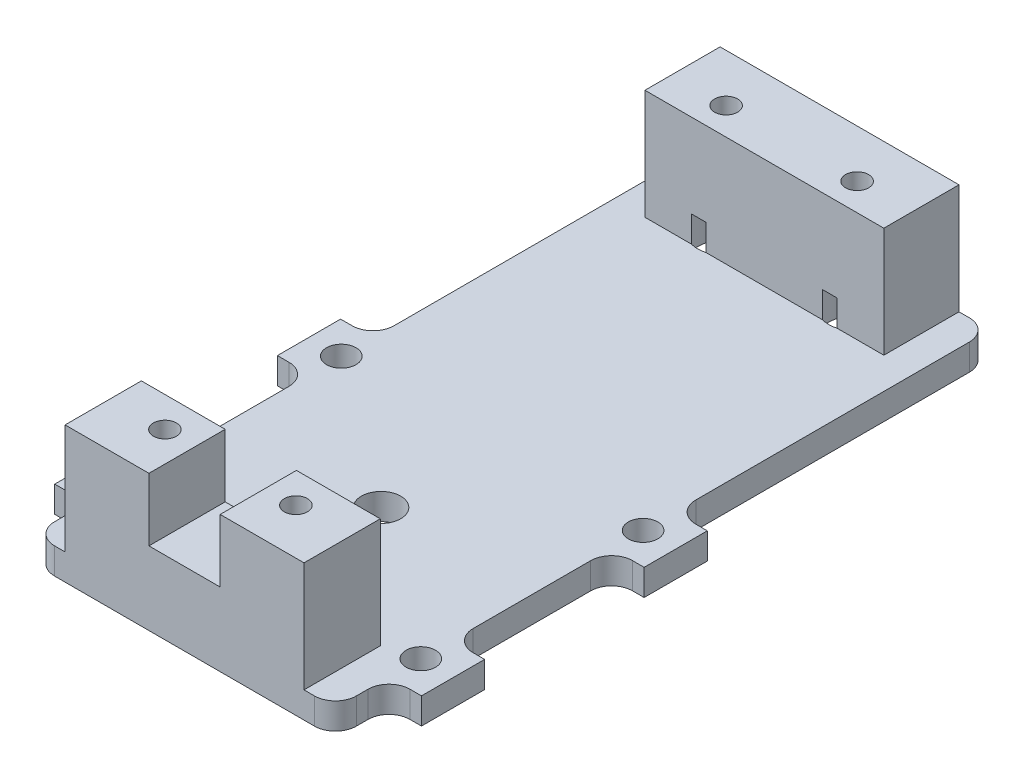
SolidWorks part; units mm, degrees
material "ABS"
ref_plane "Front Plane" through (0, 0, 0) normal (0, 0, 1) x (1, 0, 0)
ref_plane "Top Plane" through (0, 0, 0) normal (0, 1, 0) x (1, 0, 0)
ref_plane "Right Plane" through (0, 0, 0) normal (1, 0, 0) x (0, 0, -1)
sketch "Sketch1" plane through (0, 0, 0) normal (0, 1, 0) x (1, 0, 0)
  line L0 (18.288, -9.6647) -> (22.225, -9.6647)
  line L1 (-18.288, -23.8125) -> (18.288, -23.8125)
  line L2 (-18.288, -23.8125) -> (-18.288, -17.3228)
  line L3 (-18.288, 55.5625) -> (18.288, 55.5625)
  line L4 (18.288, -23.8125) -> (18.288, -17.3228)
  line L5 (-22.225, -17.3228) -> (-18.288, -17.3228)
  line L6 (-22.225, -17.3228) -> (-22.225, -9.6647)
  line L7 (-22.225, 17.3228) -> (-18.288, 17.3228)
  line L8 (22.225, -17.3228) -> (22.225, -9.6647)
  line L9 (0, 0.0043) -> (-31.7584, 0.0043) construction
  line L10 (-31.7584, 0.0043) -> (-18.288, -13.4661) construction
  line L11 (-22.225, -9.6647) -> (-18.288, -9.6647)
  line L12 (-18.288, 17.3228) -> (-18.288, 55.5625)
  line L13 (-22.225, 9.6647) -> (-18.288, 9.6647)
  line L14 (-18.288, -9.6647) -> (-18.288, 9.6647)
  line L15 (18.288, 9.6647) -> (22.225, 9.6647)
  line L17 (18.288, -9.6647) -> (18.288, 9.6647)
  line L18 (22.225, 9.6647) -> (22.225, 17.3228)
  line L19 (-22.225, 9.6647) -> (-22.225, 17.3228)
  line L20 (-18.288, -9.6647) -> (-18.288, 9.6647)
  line L21 (18.288, -9.6647) -> (18.288, 9.6647)
  line L22 (18.288, 17.3228) -> (18.288, 55.5625)
  line L23 (18.288, 17.3228) -> (22.225, 17.3228)
  line L24 (18.288, -17.3228) -> (22.225, -17.3228)
  line L25 (-31.7584, 0.0043) -> (-18.288, 13.4747) construction
  line L26 (0, -23.8125) -> (0, 0.0043) construction
  line L28 (-14.478, -13.8906) -> (14.478, -13.8906) construction
  line L29 (-14.478, -13.8906) -> (-14.478, 45.7994) construction
  line L30 (-14.478, 45.7994) -> (14.478, 45.7994) construction
  line L31 (14.478, -13.8906) -> (14.478, 45.7994) construction
  circle A0 centre (0, 0.0043) radius 2.3812
  circle A1 centre (7.9375, 49.7649) radius 3.429 construction
  circle A2 centre (-7.9375, 49.7649) radius 3.429 construction
  circle A3 centre (7.9375, -18.2563) radius 3.429 construction
  circle A4 centre (-7.9375, -18.2563) radius 3.429 construction
  point P4 (-7.9375, -18.2562)
  point P6 (0, 0)
  point P9 (7.9375, -18.2562)
  point P10 (-7.9375, 49.7649)
  point P11 (7.9375, 49.7649)
  point P31 (18.288, -13.4661)
  point P32 (18.288, 13.4747)
  point P47 (0.4762, -4.2035)
  dimension "D21" = 6.858
  dimension "D1" = 36.576
  dimension "D2" = 79.375
  dimension "D3" = 18.288
  dimension "D4" = 23.8125
  dimension "D5" = 18.2562
  dimension "D6" = 7.9375
  dimension "D9" = 5.5563
  dimension "D10" = 34.6456
  dimension "D11" = 44.45
  dimension "D12" = 19.3294
  dimension "D13" = 9.6647
  dimension "D14" = 19.05
  dimension "D15" = 19.05
  dimension "D16" = 90
  dimension "D17" = 28.956
  dimension "D18" = 14.478
  dimension "D19" = 59.69
  dimension "D20" = 13.8906
  dimension "D7" = 2
  dimension "D8" = 2
extrude "Boss-Extrude1" add sketch "Sketch1" along normal blind 3.175 contours L4 L24 L8 L0 L17 L15 L18 L23 L22 L3 L12 L7 L19 L13 L14 L11 L6 L5 L2 L1 L31 L28 L29 L30 region at (0, 0, -15.3322)
hole_wizard "9/64 (0.14063) Diameter Hole1" positions "Sketch5" profile "Sketch6" hole size "9/64" standard "Ansi Inch" end condition up to next
sketch "Sketch5" plane through (0, 0, 0) normal (0, -1, 0) x (1, 0, 0)
  point P4 (18.288, -13.4747)
  point P7 (18.288, 13.4661)
  point P35 (-18.288, -13.4704)
  point P37 (-18.288, 13.4704)
sketch "Sketch6" plane through (18.288, 0, -13.4747) normal (1, 0, 0) x (0, 0, -1)
  line L0 (0, 0) -> (0, 3.175)
  line L1 (0, 3.175) -> (1.786, 3.175)
  line L2 (1.786, 3.175) -> (1.786, 0)
  line L5 (1.786, 0) -> (0, 0)
  line L11 (0, -6.35) -> (0, 107.95) construction
  dimension "Thru Hole Dia." = 3.572
  dimension "Thru Hole Depth" = 3.175
fillet "Fillet1" radius 2.54 12 edges at (18.288, 1.5875, 23.8125) (18.288, 1.5875, 17.3228) (18.288, 1.5875, 9.6647) (18.288, 1.5875, -9.6647) (18.288, 1.5875, -17.3228) (18.288, 1.5875, -55.5625) (-18.288, 1.5875, -55.5625) (-18.288, 1.5875, -17.3228) (-18.288, 1.5875, -9.6647) (-18.288, 1.5875, 9.6647) (-18.288, 1.5875, 17.3228) (-18.288, 1.5875, 23.8125)
sketch "Sketch9" plane through (0, 0, 0) normal (0, 1, 0) x (1, 0, 0)
  line L0 (-18.288, 55.5625) -> (18.288, 55.5625) construction
  line L1 (-18.288, -23.8125) -> (18.288, -23.8125) construction
  line L5 (-14.478, -14.5696) -> (14.478, -14.5696)
  line L6 (-14.478, -14.5696) -> (-14.478, -23.8125)
  line L8 (-14.4653, 46.453) -> (14.4907, 46.453)
  line L9 (-14.4653, 46.453) -> (-14.4653, 55.5625)
  line L10 (-14.4653, 55.5625) -> (14.4907, 55.5625)
  line L11 (14.4907, 46.453) -> (14.4907, 55.5625)
  line L12 (-14.478, -23.8125) -> (14.478, -23.8125)
  line L13 (14.478, -14.5696) -> (14.478, -23.8125)
  circle A2 centre (-7.9375, -18.2562) radius 1.397
  circle A3 centre (7.9375, -18.2562) radius 1.397
  circle A4 centre (-7.9375, 49.7649) radius 1.397
  circle A5 centre (7.9375, 49.7649) radius 1.397
  dimension "D1" = 2.794
  dimension "D2" = 2.794
  dimension "D3" = 2.794
  dimension "D4" = 2.794
  dimension "D5" = 9.1095
  dimension "D7" = 28.956
  dimension "D8" = 9.2429
extrude "Boss-Extrude3" add sketch "Sketch9" along normal blind 16.51
sketch "Sketch10" plane through (0, 0, 0) normal (0, -1, 0) x (1, 0, 0)
  circle A0 centre (7.9375, 18.2562) radius 3.429
  circle A1 centre (-7.9375, 18.2562) radius 3.429
  circle A2 centre (7.9375, -49.7649) radius 3.429
  circle A3 centre (-7.9375, -49.7649) radius 3.429
extrude "Cut-Extrude1" cut sketch "Sketch10" against normal blind 6.35
sketch "Sketch11" plane through (0, 16.51, 0) normal (0, 1, 0) x (1, 0, 0)
  line L1 (-4.318, -14.5696) -> (4.318, -14.5696)
  line L2 (-4.318, -14.5696) -> (-4.318, -23.8125)
  line L3 (-4.318, -23.8125) -> (4.318, -23.8125)
  line L4 (4.318, -14.5696) -> (4.318, -23.8125)
  line L5 (-14.478, -14.5696) -> (-14.478, -23.8125) construction
  line L6 (14.478, -23.8125) -> (14.478, -14.5696) construction
  point P7 (-14.478, -19.191)
  dimension "D1" = 8.636
  dimension "D2" = 10.16
  dimension "D3" = 10.16
extrude "Cut-Extrude2" cut sketch "Sketch11" against normal blind 7.62
